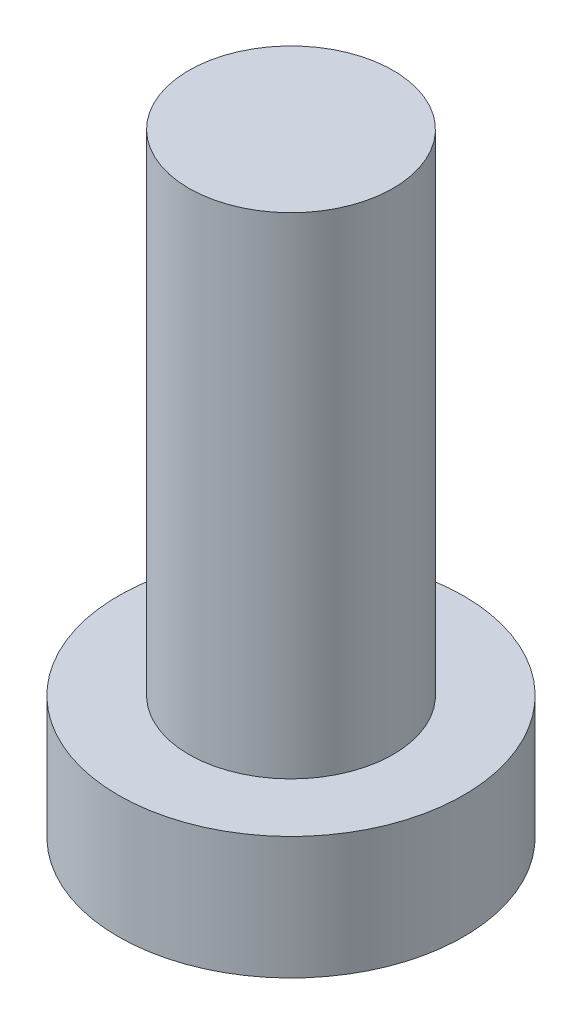
SolidWorks part; units mm, degrees
ref_plane "Front Plane" through (0, 0, 0) normal (0, 0, 1) x (1, 0, 0)
ref_plane "Top Plane" through (0, 0, 0) normal (0, 1, 0) x (1, 0, 0)
ref_plane "Right Plane" through (0, 0, 0) normal (1, 0, 0) x (0, 0, -1)
sketch "Sketch1" plane through (0, 0, 0) normal (0, 1, 0) x (1, 0, 0)
  circle A0 centre (0, 0) radius 4.225
  circle A1 centre (0, 0) radius 2.5
  dimension "D1" = 5
extrude "Boss-Extrude1" add sketch "Sketch1" along normal blind 3
extrude "Boss-Extrude2" add sketch "Sketch1<2>" along normal blind 15 contours A1 region at (0, 0, 0)
sketch "Sketch1<2>" plane through (0, 0, 0) normal (0, 1, 0) x (1, 0, 0) same geometry as "Sketch1"
